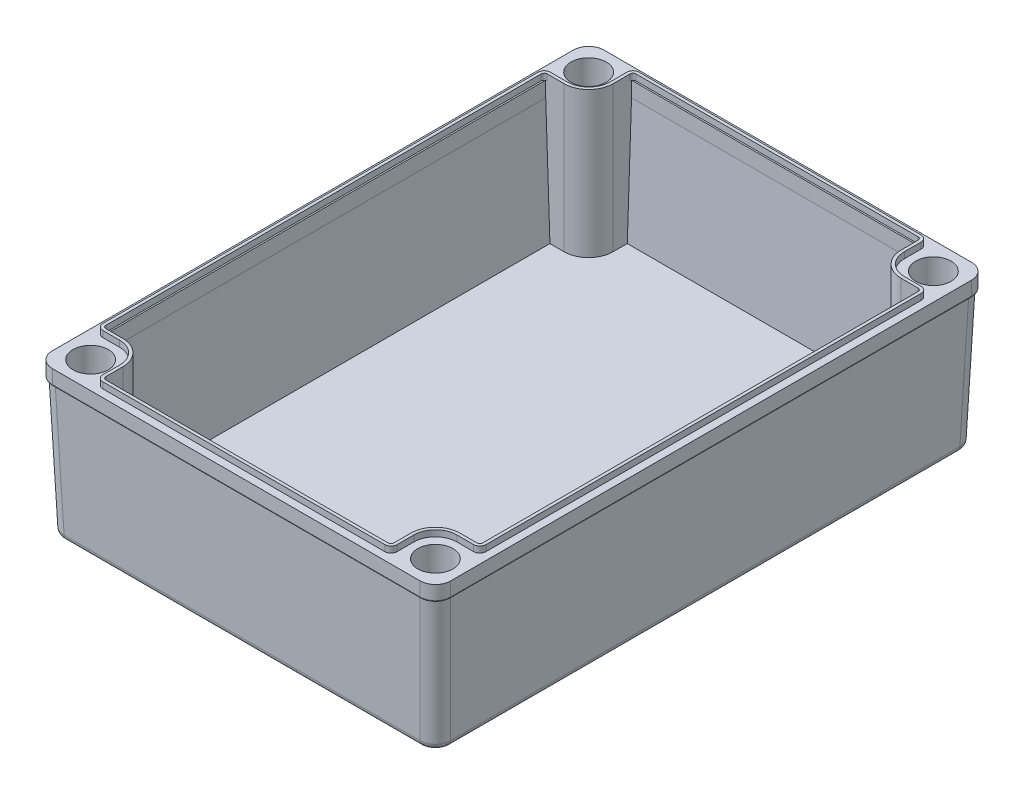
SolidWorks part; units mm, degrees
ref_plane "FRONT" through (0, 0, 0) normal (0, 0, 1) x (1, 0, 0)
ref_plane "TOP" through (0, 0, 0) normal (0, 1, 0) x (1, 0, 0)
ref_plane "SIDE" through (0, 0, 0) normal (1, 0, 0) x (0, 0, -1)
sketch "Sketch1" plane through (0, 0, 0) normal (0, 1, 0) x (1, 0, 0)
  line L1 (-63, -88) -> (63, -88)
  line L2 (-63, -88) -> (-63, 88)
  line L3 (-63, 88) -> (63, 88)
  line L4 (63, -88) -> (63, 88)
  line L5 (-63, -88) -> (63, 88) construction
  line L6 (-63, 88) -> (63, -88) construction
  point P0 (0, 0)
  dimension "D1" = 176
  dimension "D2" = 126
extrude "Boss-Extrude1" add sketch "Sketch1" along normal blind 44
draft "Draft1" type of draft neutral plane draft angle 1.953 faces to draft 4 face at (-63, 22, 0) face at (0, 22, -88) face at (63, 22, 0) face at (0, 22, 88) neutral plane through (0, 0, 0) neutral plane normal (0, -1, 0) parameters "D1"=1.953
shell "Shell2" thickness 3.5 removed face at (0, 44, 0)
sketch "Sketch2" plane through (0, 44, 0) normal (0, 1, 0) x (1, 0, 0)
  line L2 (-60.9983, 85.9983) -> (-60.9983, -85.9983) construction
  line L3 (-65, -90) -> (65, -90)
  line L4 (-65, -90) -> (-65, 90)
  line L5 (-65, 90) -> (65, 90)
  line L6 (65, -90) -> (65, 90)
  line L7 (-65, -90) -> (65, 90) construction
  line L8 (-65, 90) -> (65, -90) construction
  point P4 (0, 0)
  line M1 (64.5004, -89.5004) -> (64.5004, 89.5004)
  line M2 (64.5004, 89.5004) -> (-64.5004, 89.5004)
  line M3 (-64.5004, 89.5004) -> (-64.5004, -89.5004)
  line M4 (-64.5004, -89.5004) -> (64.5004, -89.5004)
  line M13 (60.9983, 85.9983) -> (60.9983, -85.9983)
  line M14 (60.9983, -85.9983) -> (-60.9983, -85.9983)
  line M15 (-60.9983, -85.9983) -> (-60.9983, 85.9983)
  line M16 (-60.9983, 85.9983) -> (60.9983, 85.9983)
  dimension "D1" = 130
  dimension "D2" = 180
extrude "Boss-Extrude2" add sketch "Sketch2" along normal blind 5 contours M4 M1 M2 M3 M16 M13 M14 M15 | L3 L6 L5 L4 M1 M4 M3 M2 region at (-64.778, 44, 0) region at (0, 44, 87.294)
sketch "Sketch3" plane through (0, 49, 0) normal (0, 1, 0) x (1, 0, 0)
  line L0 (-55, 72) -> (-61.4983, 72)
  line L1 (-56.25, -81.25) -> (56.25, -81.25) construction
  line L2 (-56.25, -81.25) -> (-56.25, 81.25) construction
  line L3 (-56.25, 81.25) -> (56.25, 81.25) construction
  line L4 (56.25, -81.25) -> (56.25, 81.25) construction
  line L5 (-56.25, -81.25) -> (56.25, 81.25) construction
  line L6 (-56.25, 81.25) -> (56.25, -81.25) construction
  line L7 (-47, 80) -> (-47, 86.4983)
  line L8 (55, 72) -> (61.4983, 72)
  line L9 (-55, -80) -> (55, -80) construction
  line L10 (-55, -80) -> (-55, 80) construction
  line L11 (-55, 80) -> (55, 80) construction
  line L12 (60.9983, 85.9983) -> (-60.9983, 85.9983)
  line L13 (60.9983, -85.9983) -> (60.9983, 85.9983)
  line L14 (-60.9983, -85.9983) -> (60.9983, -85.9983)
  line L15 (-60.9983, 85.9983) -> (-60.9983, -85.9983)
  line L16 (60.9983, 85.9983) -> (-60.9983, 85.9983)
  line L17 (60.9983, -85.9983) -> (60.9983, 85.9983)
  line L18 (-60.9983, -85.9983) -> (60.9983, -85.9983)
  line L19 (-60.9983, 85.9983) -> (-60.9983, -85.9983)
  line L20 (55, -80) -> (55, 80) construction
  line L21 (-55, -80) -> (55, 80) construction
  line L22 (-55, 80) -> (55, -80) construction
  line L23 (61.4983, -86.4983) -> (61.4983, 86.4983)
  line L24 (61.4983, 86.4983) -> (-61.4983, 86.4983)
  line L25 (-61.4983, 86.4983) -> (-61.4983, -86.4983)
  line L26 (-61.4983, -86.4983) -> (61.4983, -86.4983)
  line L27 (47, 80) -> (47, 86.4983)
  line L28 (-47, -80) -> (-47, -86.4983)
  line L29 (-55, -72) -> (-61.4983, -72)
  line L30 (47, -80) -> (47, -86.4983)
  line L31 (55, -72) -> (61.4983, -72)
  arc A0 (47, 80) -> (55, 72) centre (55, 80) ccw
  arc A1 (-55, -72) -> (-47, -80) centre (-55, -80) cw
  arc A2 (-55, 72) -> (-47, 80) centre (-55, 80) ccw
  arc A3 (47, -80) -> (55, -72) centre (55, -80) cw
  point P0 (0, 0)
  point P6 (0, 0)
  line M18 (-60.9983, 85.9983) -> (60.9983, 85.9983)
  line M19 (60.9983, 85.9983) -> (60.9983, -85.9983)
  line M20 (60.9983, -85.9983) -> (-60.9983, -85.9983)
  line M21 (-60.9983, -85.9983) -> (-60.9983, 85.9983)
  dimension "D7" = 8
  dimension "D1" = 112.5
  dimension "D2" = 162.5
  dimension "D4" = 160
  dimension "D5" = 110
  dimension "D3" = 0
  dimension "D6" = 0.5
extrude "Boss-Extrude3" add sketch "Sketch3" against normal up to surface (45.5 mm away) contours L0 A2 L7 M18 M21 | L27 A0 L8 L16 M19 | A3 L30 L17 L31 M20 | A1 L29 L18 L28 M21 region at (-54.392, 49, -79.392) region at (-54.392, 49, 79.392) region at (54.392, 49, -79.392) region at (54.392, 49, 79.392) up to face at (0, 3.5, 0)
hole_wizard "CBORE for M4 SBHCS1" positions "Sketch5" profile "Sketch4" counterbore size "M4" standard "ANSI Metric" end condition through all
sketch "Sketch5" plane through (0, 49, 0) normal (0, 1, 0) x (1, 0, 0)
  point P0 (-56.25, -81.25)
  point P3 (56.25, -81.25)
  point P6 (56.25, 81.25)
  point P9 (-56.25, 81.25)
sketch "Sketch4" plane through (-56.25, 49, 81.25) normal (1, 0, 0) x (0, 0, 1)
  line L0 (0, 0) -> (0, 49)
  line L1 (0, 49) -> (2.25, 49)
  line L3 (2.25, 49) -> (2.25, 46)
  line L4 (2.25, 46) -> (5.75, 46)
  line L5 (5.75, 46) -> (5.75, 0)
  line L7 (5.75, 0) -> (0, 0)
  line L11 (0, -6.35) -> (0, 107.95) construction
  dimension "Thru Hole Dia." = 4.5
  dimension "Thru Hole Depth" = 49
  dimension "C'Bore Dia." = 11.5
  dimension "C'Bore Depth" = 46
sketch "Sketch7" plane through (0, 49, 0) normal (0, 1, 0) x (1, 0, 0)
  line L0 (-55, 72) -> (-61.4983, 72) construction
  line L1 (-47, 80) -> (-47, 86.4983) construction
  line L2 (-61.4983, 86.4983) -> (-61.4983, -86.4983) construction
  line L3 (61.4983, 86.4983) -> (-61.4983, 86.4983) construction
  line L4 (47, 80) -> (47, 86.4983) construction
  line L5 (55, 72) -> (61.4983, 72) construction
  line L6 (61.4983, -86.4983) -> (61.4983, 86.4983) construction
  line L7 (55, -72) -> (61.4983, -72) construction
  line L8 (47, -80) -> (47, -86.4983) construction
  line L9 (-61.4983, -86.4983) -> (61.4983, -86.4983) construction
  line L10 (-47, -80) -> (-47, -86.4983) construction
  line L11 (-55, -72) -> (-61.4983, -72) construction
  line L12 (-55, 72) -> (-60.4983, 72)
  line L13 (-47, 80) -> (-47, 85.4983)
  line L14 (-61.4983, 71) -> (-61.4983, -71)
  line L15 (46, 86.4983) -> (-46, 86.4983)
  line L16 (47, 80) -> (47, 85.4983)
  line L17 (55, 72) -> (60.4983, 72)
  line L18 (61.4983, -71) -> (61.4983, 71)
  line L19 (55, -72) -> (60.4983, -72)
  line L20 (47, -80) -> (47, -85.4983)
  line L21 (-46, -86.4983) -> (46, -86.4983)
  line L22 (-47, -80) -> (-47, -85.4983)
  line L23 (-55, -72) -> (-60.4983, -72)
  arc A0 (-55, 72) -> (-47, 80) centre (-55, 80) ccw construction
  arc A1 (47, 80) -> (55, 72) centre (55, 80) ccw construction
  arc A2 (55, -72) -> (47, -80) centre (55, -80) ccw construction
  arc A3 (-47, -80) -> (-55, -72) centre (-55, -80) ccw construction
  arc A4 (-55, 72) -> (-47, 80) centre (-55, 80) ccw
  arc A5 (47, 80) -> (55, 72) centre (55, 80) ccw
  arc A6 (55, -72) -> (47, -80) centre (55, -80) ccw
  arc A7 (-47, -80) -> (-55, -72) centre (-55, -80) ccw
  arc A8 (-60.4983, -72) -> (-61.4983, -71) centre (-60.4983, -71) cw
  arc A9 (-47, -85.4983) -> (-46, -86.4983) centre (-46, -85.4983) ccw
  arc A10 (47, -85.4983) -> (46, -86.4983) centre (46, -85.4983) cw
  arc A11 (60.4983, -72) -> (61.4983, -71) centre (60.4983, -71) ccw
  arc A12 (60.4983, 72) -> (61.4983, 71) centre (60.4983, 71) cw
  arc A13 (47, 85.4983) -> (46, 86.4983) centre (46, 85.4983) ccw
  arc A14 (-60.4983, 72) -> (-61.4983, 71) centre (-60.4983, 71) ccw
  arc A15 (-47, 85.4983) -> (-46, 86.4983) centre (-46, 85.4983) cw
  dimension "D1" = 1
extrude "Extrude-Thin1" add sketch "Sketch7" along normal blind 2 thin thin type one direction wall 1
fillet "Fillet2" radius 5 8 edges at (63.7502, 22, -88.7502) (-63.7502, 22, -88.7502) (63.7502, 22, 88.7502) (-63.7502, 22, 88.7502) (65, 46.5, 90) (-65, 46.5, 90) (-65, 46.5, -90) (65, 46.5, -90)
fillet "Fillet4" radius 2 8 edges at (-61.5367, 0, 86.5367) (-63, 0, 0) (-61.5367, 0, -86.5367) (0, 0, -88) (61.5367, 0, -86.5367) (63, 0, 0) (61.5367, 0, 86.5367) (0, 0, 88)
fillet "Fillet5" radius 0.5 8 edges at (-63.5355, 44, 88.5355) (-65, 44, 0) (-63.5355, 44, -88.5355) (0, 44, -90) (63.5355, 44, -88.5355) (65, 44, 0) (63.5355, 44, 88.5355) (0, 44, 90)
sketch "Sketch8" plane through (0, 0, 0) normal (0, 1, 0) x (1, 0, 0)
  line L0 (0, 70) -> (0, -70) construction
  line L1 (-45, -50) -> (45, -50) construction
  line L2 (-45, -50) -> (-45, 50) construction
  line L3 (-45, 50) -> (45, 50) construction
  line L4 (45, -50) -> (45, 50) construction
  line L5 (-45, -50) -> (45, 50) construction
  line L6 (-45, 50) -> (45, -50) construction
  line L7 (0, -28.05) -> (0, 28.05) construction
  circle A0 centre (0, 70) radius 5
  circle A1 centre (-45, 50) radius 5
  circle A2 centre (-45, 0) radius 5
  circle A3 centre (-45, -50) radius 5
  circle A4 centre (0, -70) radius 5
  circle A5 centre (45, -50) radius 5
  circle A6 centre (45, 0) radius 5
  circle A7 centre (45, 50) radius 5
  circle A8 centre (-56.25, -81.25) radius 5
  circle A9 centre (56.25, -81.25) radius 5
  circle A10 centre (56.25, 81.25) radius 5
  circle A11 centre (-56.25, 81.25) radius 5
  circle A12 centre (-56.25, 81.25) radius 2.25 construction
  circle A13 centre (56.25, 81.25) radius 2.25 construction
  circle A14 centre (-56.25, -81.25) radius 2.25 construction
  circle A15 centre (56.25, -81.25) radius 2.25 construction
  circle A16 centre (-56.25, 81.25) radius 2.25
  circle A17 centre (56.25, 81.25) radius 2.25
  circle A18 centre (-56.25, -81.25) radius 2.25
  circle A19 centre (56.25, -81.25) radius 2.25
  point P0 (0, 0)
  dimension "D4" = 10
  dimension "D5" = 10
  dimension "D1" = 140
  dimension "D2" = 100
  dimension "D3" = 90
extrude "Boss-Extrude4" add sketch "Sketch8" against normal blind 1
fillet "Fillet6" radius 1 12 edges at (56.25, -1, 86.25) (0, -1, 75) (45, -1, 55) (45, -1, 5) (56.25, -1, -76.25) (45, -1, -45) (0, -1, -65) (-56.25, -1, -76.25) (-45, -1, -45) (-45, -1, 5) (-45, -1, 55) (-56.25, -1, 86.25)
